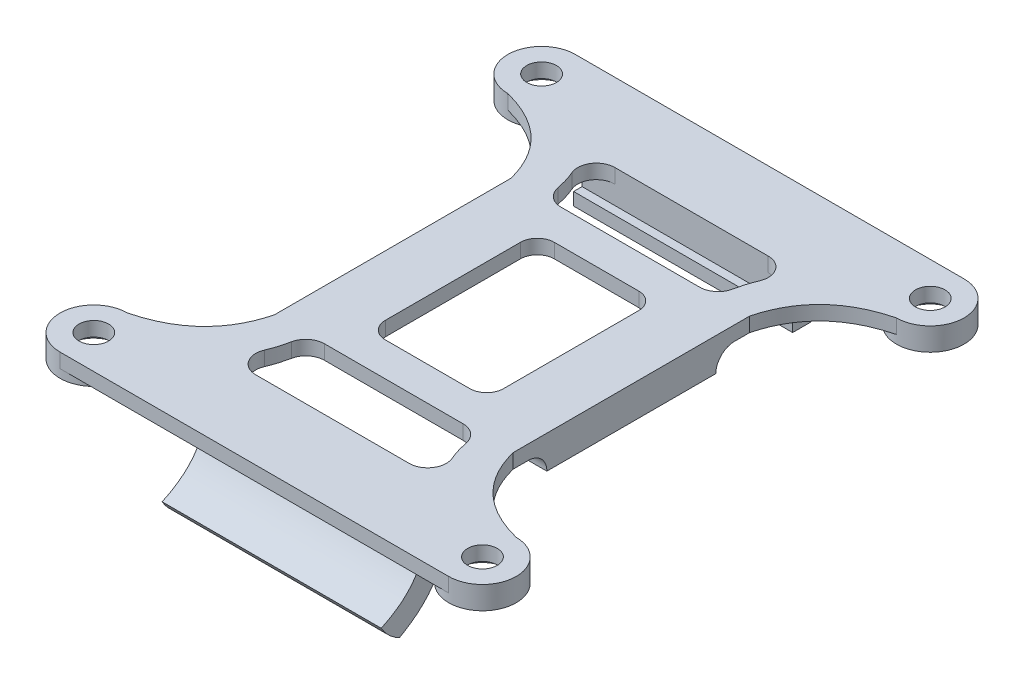
SolidWorks part; units mm, degrees
ref_plane "Front Plane" through (0, 0, 0) normal (0, 0, 1) x (1, 0, 0)
ref_plane "Top Plane" through (0, 0, 0) normal (0, 1, 0) x (1, 0, 0)
ref_plane "Right Plane" through (0, 0, 0) normal (1, 0, 0) x (0, 0, -1)
sketch "Sketch1" plane through (0, 0, 0) normal (0, 1, 0) x (1, 0, 0)
  line L0 (0, 14.1954) -> (0, -8.337) construction
  line L1 (-16.0431, 0) -> (15.1418, 0) construction
  line L2 (-23, 30.5) -> (23, 30.5)
  line L3 (-23, 22.5) -> (23, 22.5)
  line L4 (-23, -22.5) -> (23, -22.5)
  line L5 (-23, -30.5) -> (23, -30.5)
  line L6 (-14.125, 14) -> (-14.125, -14)
  line L7 (-10.125, 10) -> (10.125, 10)
  line L8 (-10.125, 10) -> (-10.125, -10)
  line L9 (-10.125, -10) -> (10.125, -10)
  line L10 (10.125, 10) -> (10.125, -10)
  line L11 (-10.125, 10) -> (10.125, -10) construction
  line L12 (-10.125, -10) -> (10.125, 10) construction
  line L13 (-14.125, -14) -> (14.125, -14)
  line L14 (14.125, 14) -> (14.125, -14)
  line L15 (-14.125, 14) -> (14.125, 14)
  line L16 (-14.125, 14) -> (-14.125, 22.5) construction
  line L17 (14.125, 14) -> (14.125, 22.5) construction
  line L18 (-14.125, 18.25) -> (14.125, 18.25) construction
  line L19 (-10.125, 10) -> (-10.125, 14) construction
  line L20 (-12.9623, 21.25) -> (12.9623, 21.25)
  line L21 (-12.9623, -21.25) -> (12.9623, -21.25)
  circle A0 centre (-23, 26.5) radius 1.75
  circle A1 centre (23, 26.5) radius 1.75
  circle A2 centre (23, -26.5) radius 1.75
  circle A3 centre (-23, -26.5) radius 1.75
  circle A4 centre (-23, 26.5) radius 4
  circle A5 centre (23, 26.5) radius 4
  circle A6 centre (23, -26.5) radius 4
  circle A7 centre (-23, -26.5) radius 4
  spline S0 degree 2 poles (-23, 22.5) (-15.8481, 20.6717) (-14.125, 14) knots 0 0 0 1 1 1
  spline S1 degree 2 poles (-10.125, 14) (-10.4618, 18.9985) (-14.125, 22.5) knots 0 0 0 1 1 1
  spline S2 degree 2 poles (23, 22.5) (15.8481, 20.6717) (14.125, 14) knots 0 0 0 1 1 1
  spline S3 degree 2 poles (10.125, 14) (10.4618, 18.9985) (14.125, 22.5) knots 0 0 0 1 1 1
  spline S4 degree 2 poles (23, -22.5) (15.8481, -20.6717) (14.125, -14) knots 0 0 0 1 1 1
  spline S5 degree 2 poles (10.125, -14) (10.4618, -18.9985) (14.125, -22.5) knots 0 0 0 1 1 1
  spline S6 degree 2 poles (-10.125, -14) (-10.4618, -18.9985) (-14.125, -22.5) knots 0 0 0 1 1 1
  spline S7 degree 2 poles (-23, -22.5) (-15.8481, -20.6717) (-14.125, -14) knots 0 0 0 1 1 1
  point P25 (0, 0)
  dimension "D1" = 3.5
  dimension "D4" = 8
  dimension "D2" = 46
  dimension "D3" = 53
  dimension "D5" = 20
  dimension "D6" = 20.25
  dimension "D8" = 2
  dimension "D9" = 5
  dimension "D10" = 42.5
  dimension "D7" = 4
extrude "Boss-Extrude1" add sketch "Sketch1" along normal blind 1.7 contours L3 A5 L2 A4 | A4 A0 | A5 A1 | S3 L15 S2 L3 | L15 S1 L3 S0 | L15 L6 L13 L14 L7 L10 L9 L8 | S7 L4 S6 L13 | L13 S5 L4 S4 | L4 A7 L5 A6 | A6 A2 | A7 A3 | L20 S3 L3 S1 | L21 S6 L4 S5 region at (0, 0, -26.5) region at (-20.2516, 0, -29.2484) region at (25.7484, 0, -29.2484) region at (-14.5143, 0, -18.7549) region at (14.5143, 0, -18.7549) region at (0, 0, -21.884) region at (-12.125, 0, -13.6022) region at (-14.5143, 0, 18.7549) region at (14.5143, 0, 18.7549) region at (0, 0, 26.5) region at (-20.2516, 0, 23.7516) region at (25.7484, 0, 23.7516) region at (0, 0, 21.884)
sketch "Sketch2" plane through (0, 0, 0) normal (0, -1, 0) x (1, 0, 0)
  line L0 (-14.125, -14) -> (-14.125, 14) construction
  line L1 (-10.125, 10) -> (-14.125, 10)
  line L2 (-10.125, 10) -> (-10.125, -10)
  line L3 (-10.125, -10) -> (-14.125, -10)
  line L4 (-14.125, 10) -> (-14.125, -10)
  line L5 (-10.125, -10) -> (10.125, -10) construction
  line L6 (14.125, -14) -> (14.125, 14) construction
  line L7 (10.125, 10) -> (14.125, 10)
  line L8 (10.125, 10) -> (10.125, -10)
  line L9 (10.125, -10) -> (14.125, -10)
  line L10 (14.125, 10) -> (14.125, -10)
  line L11 (-14.125, 0) -> (14.125, 0) construction
  line L12 (-12.9623, 21.25) -> (12.9623, 21.25)
  line L13 (-12.9623, 21.25) -> (-12.9623, 23.25)
  line L14 (-12.9623, 23.25) -> (12.9623, 23.25)
  line L15 (12.9623, 21.25) -> (12.9623, 23.25)
  line L17 (-12.9623, -21.25) -> (12.9623, -21.25)
  line L18 (-12.9623, -21.25) -> (-12.9623, -23.25)
  line L19 (-12.9623, -23.25) -> (12.9623, -23.25)
  line L20 (12.9623, -21.25) -> (12.9623, -23.25)
  dimension "D1" = 2
  dimension "D2" = 2
extrude "Boss-Extrude2" add sketch "Sketch2" along normal blind 2.2
sketch "Sketch4" plane through (0, -2.2, 0) normal (0, -1, 0) x (1, 0, 0)
  line L0 (12.9623, 21.25) -> (12.9623, 23.25) construction
  line L1 (-12.9623, 28.45) -> (12.9623, 28.45)
  line L2 (-12.9623, 28.45) -> (-12.9623, 20.45)
  line L3 (-12.9623, 20.45) -> (12.9623, 20.45)
  line L4 (12.9623, 28.45) -> (12.9623, 20.45)
  line L5 (-12.9623, 21.25) -> (12.9623, 21.25) construction
  line L13 (-12.9623, 23.25) -> (-12.9623, 21.25) construction
  line M1 (-12.9623, 23.25) -> (-12.9623, 21.25)
  line M2 (-12.9623, 21.25) -> (12.9623, 21.25)
  line M3 (12.9623, 21.25) -> (12.9623, 23.25)
  line M4 (12.9623, 23.25) -> (-12.9623, 23.25)
  dimension "D1" = 0.8
  dimension "D2" = 8
extrude "Boss-Extrude4" add sketch "Sketch4" along normal blind 10 contours L4 L1 L2 M4 | M4 M1 M2 M3 | L4 L2 L3 M2 region at (0, -2.2, 25.85) region at (0, -2.2, 22.25) region at (0, -2.2, 20.85)
sketch "Sketch5" plane through (12.9623, 0, 0) normal (1, 0, 0) x (0, 0, -1)
  line L0 (-20.45, -12.2) -> (-20.45, -2.2) construction
  line L1 (0, 1.7) -> (0, -2.2) construction
  line L2 (-28.45, -2.2) -> (-20.45, -2.2)
  line L3 (-28.45, -2.2) -> (-28.45, -12.2)
  line L4 (-28.45, -12.2) -> (-20.45, -12.2)
  line L5 (-20.45, -2.2) -> (-20.45, -12.2)
  line L6 (14, 1.7) -> (-14, 1.7) construction
  line L7 (10, -2.2) -> (-10, -2.2) construction
  line L8 (-28.45, -12.2) -> (-20.45, -12.2) construction
  line L9 (-28.45, -12.2) -> (-28.45, -2.2) construction
  spline S0 degree 2 poles (-23.25, -2.2) (-23.25, -7.2897) (-28.45, -9.6504) knots 0 0 0 1 1 1
  spline S1 degree 1 poles (-20.45, -2.2) (-27.2926, -12.2) knots 0 0 1 1 construction
  spline S2 degree 3 poles (-20.45, -2.2) (-20.45, -3.2656) (-20.7288, -5.4274) (-22.1106, -8.3045) (-23.9788, -10.2297) (-25.7739, -11.4469) (-26.7826, -11.9685) (-27.2926, -12.2) knots 0 0 0 0 0.25 0.5 0.75 0.875 1 1 1 1
  line M4 (-28.45, -2.2) -> (-28.45, -12.2)
  line M6 (-20.45, -12.2) -> (-20.45, -2.2)
  line M25 (-23.25, -2.2) -> (-28.45, -2.2)
extrude "Cut-Extrude1" cut sketch "Sketch5" against normal up to next contours M25 M4 | L4 M6 region at (12.9623, -5.1574, 26.2828) region at (12.9623, -9.9325, 22.3429)
fillet "Fillet2" radius 2.2 12 edges at (-12.9623, 0.85, -21.25) (12.9623, 0.85, -21.25) (-10.125, 0.85, -14) (10.125, 0.85, -14) (-12.9623, 0.85, 21.25) (-10.125, 0.85, 14) (10.125, 0.85, 14) (12.9623, 0.85, 21.25) (12.125, 0, 10) (12.125, 0, -10)
sketch "Sketch7" plane through (0, 0, 0) normal (0, -1, 0) x (1, 0, 0)
  line L0 (0, 30.5) -> (0, -30.5) construction
  line L1 (-23, 30.5) -> (23, 30.5) construction
  line L2 (-23, -30.5) -> (23, -30.5) construction
  line L3 (-14.125, 0) -> (14.125, 0) construction
  line L4 (-14.125, 10) -> (-14.125, -10) construction
  line L5 (14.125, -10) -> (14.125, 10) construction
  circle A0 centre (-23, 26.5) radius 4
  arc A1 (-23, 30.5) -> (-23, 22.5) centre (-23, 26.5) ccw construction
  circle A2 centre (-23, 26.5) radius 3
  circle A3 centre (23, 26.5) radius 3
  circle A4 centre (23, 26.5) radius 4
  circle A5 centre (23, -26.5) radius 3
  circle A6 centre (23, -26.5) radius 4
  circle A7 centre (-23, -26.5) radius 4
  circle A8 centre (-23, -26.5) radius 3
  dimension "D1" = 6
extrude "Boss-Extrude5" add sketch "Sketch7" along normal blind 1
sketch "Sketch8" plane through (0, -2.2, 0) normal (0, -1, 0) x (1, 0, 0)
  line L0 (12.9623, -21.25) -> (-12.9623, -21.25) construction
  line L1 (-12.9623, -23.25) -> (12.9623, -23.25)
  line L2 (-12.9623, -23.25) -> (-12.9623, -20.25)
  line L3 (-12.9623, -20.25) -> (12.9623, -20.25)
  line L4 (12.9623, -23.25) -> (12.9623, -20.25)
  dimension "D1" = 1
extrude "Boss-Extrude6" add sketch "Sketch8" along normal blind 1.5
fillet "Fillet8" radius 1 1 edges at (0, -3.7, -23.25)
fillet "Fillet9" radius 5 1 edges at (0, -12.2, 28.45)
sketch "Sketch9" plane through (0, 1.7, 0) normal (0, 1, 0) x (1, 0, 0)
  line L0 (-10.125, -10) -> (10.125, -10) construction
  line L1 (7, 10) -> (-7, 10)
  line L2 (7, 10) -> (7, -10)
  line L3 (7, -10) -> (-7, -10)
  line L4 (-7, 10) -> (-7, -10)
  line L5 (7, 10) -> (-7, -10) construction
  line L6 (7, -10) -> (-7, 10) construction
  line L9 (10.125, 10) -> (-10.125, 10)
  line L10 (10.125, 10) -> (10.125, -10)
  line L11 (10.125, -10) -> (-10.125, -10)
  line L12 (-10.125, 10) -> (-10.125, -10)
  line L13 (10.125, 10) -> (-10.125, -10) construction
  line L14 (10.125, -10) -> (-10.125, 10) construction
  point P0 (0, 0)
  point P8 (0, 0)
  line M31 (-10.125, 10) -> (10.125, 10)
  line M32 (10.125, 10) -> (10.125, -10)
  line M33 (10.125, -10) -> (-10.125, -10)
  line M34 (-10.125, -10) -> (-10.125, 10)
  dimension "D1" = 14
extrude "Boss-Extrude7" add sketch "Sketch9" against normal up to surface (1.7 mm away) contours L4 M31 M34 M33 | L2 M31 M33 M32 region at (8.5625, 1.7, 0) region at (-8.5625, 1.7, 0) up to face at (-23, 0, -23.5)
fillet "Fillet10" radius 2 4 edges at (7, 0.85, 10) (-7, 0.85, 10) (-7, 0.85, -10) (7, 0.85, -10)
